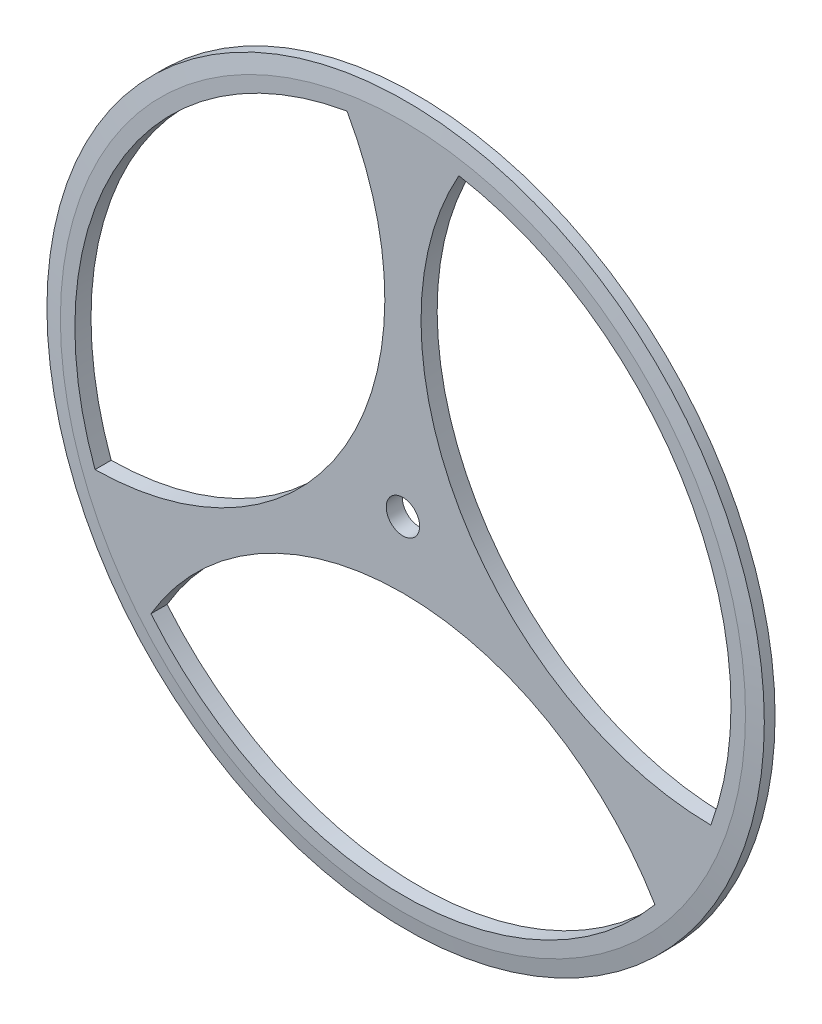
SolidWorks part; units mm, degrees
ref_plane "Alzado" through (0, 0, 0) normal (0, 0, 1) x (1, 0, 0)
ref_plane "Planta" through (0, 0, 0) normal (0, 1, 0) x (1, 0, 0)
ref_plane "Vista lateral" through (0, 0, 0) normal (1, 0, 0) x (0, 0, -1)
ref_axis "Axis1" through (0, 0, -2.5858) along (0, 0, 1)
sketch "Sketch1" plane through (0, 0, 0) normal (0, 0, 1) x (1, 0, 0)
  circle A0 centre (0, 0) radius 6.67
  dimension "D1" = 13.34
extrude "Boss-Extrude1" add sketch "Sketch1" along normal mid plane 0.3
chamfer "Chamfer1" distance 0.3 distance2 0.05 1 edges at (6.67, 0, -0.15) first distance on face at (6.67, 0, -0.15)
chamfer "Chamfer2" distance 0.05 distance2 0.3 1 edges at (6.67, 0, 0.15) first distance on face at (6.67, 0, -0.1)
sketch "Sketch2" plane through (0, 0, 0) normal (0, 0, 1) x (1, 0, 0)
  circle A0 centre (0, 0) radius 0.3105
  dimension "D1" = 0.621
extrude "Cut-Extrude1" cut sketch "Sketch2" against normal through all both and the other way through all
sketch "Sketch3" plane through (0, 0, 0) normal (0, 0, 1) x (1, 0, 0)
  line L0 (0, 0) -> (9.9371, 5.7372) construction
  line L1 (0, -1000) -> (0, 49000) construction
  line L2 (-1000, 0) -> (49000, 0) construction
  circle A1 centre (0, 0) radius 6.67
  circle A2 centre (0, 0) radius 6.67 construction
  arc A3 (1.0399, 6.0107) -> (5.7254, -2.1048) centre (5.7764, 3.335) ccw
  arc A4 (5.7254, -2.1048) -> (1.0399, 6.0107) centre (0, 0) ccw
  point P11 (5.7764, 3.335)
  dimension "D2" = 6.1
  dimension "D3" = 5.44
  dimension "D1" = 60
extrude "Cut-Extrude2" cut sketch "Sketch3" against normal through all both and the other way through all
pattern_circular "CirPattern1" count 3 over 360 about axis through (0, 0, -2.5858) along (0, 0, 1) of "Cut-Extrude2"
